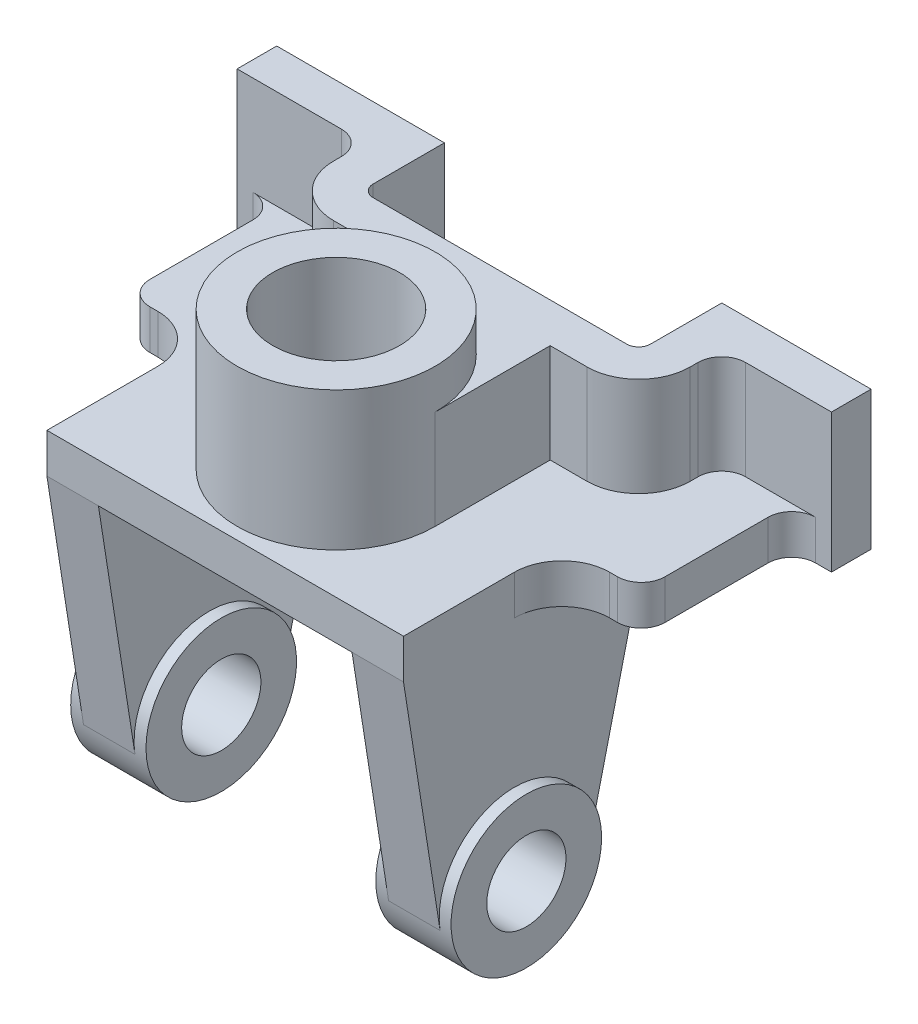
SolidWorks part; units mm, degrees
ref_plane "Front Plane" through (0, 0, 0) normal (0, 0, 1) x (1, 0, 0)
ref_plane "Top Plane" through (0, 0, 0) normal (0, 1, 0) x (1, 0, 0)
ref_plane "Right Plane" through (0, 0, 0) normal (1, 0, 0) x (0, 0, -1)
sketch "Sketch1" plane through (0, 0, 0) normal (0, 1, 0) x (1, 0, 0)
  line L1 (-45, -44) -> (45, -44)
  line L3 (-75, 44) -> (-32.6781, 44)
  line L7 (65, 2) -> (65, 28)
  line L9 (-65, 2) -> (-65, 28)
  line L10 (-71, 34) -> (-75, 34)
  line L11 (71, 34) -> (75, 34)
  line L12 (37.3219, 44) -> (75, 44)
  line L17 (65, -34) -> (65, 34) construction
  line L18 (-65, -34) -> (-65, 34) construction
  line L19 (-75, 34) -> (-71, 34)
  line L20 (-75, 44) -> (75, 44) construction
  line L22 (-65, 34) -> (65, 34) construction
  line L23 (-32.6781, 44) -> (-32.6781, 26.013)
  line L24 (-29.6781, 23.013) -> (34.3219, 23.013)
  line L25 (37.3219, 44) -> (37.3219, 26.013)
  line L26 (75, 34) -> (53.3219, 34)
  line L27 (-48.6781, 34) -> (-75, 34)
  line L28 (-59, -4) -> (-57, -4)
  line L29 (-65, 2) -> (-65, 28)
  line L31 (65, 2) -> (65, 28)
  line L32 (-75, 34) -> (-75, 44)
  line L35 (-45, -44) -> (45, -44)
  line L36 (-45, -44) -> (-45, -16)
  line L38 (45, -44) -> (45, -16)
  line L39 (75, 34) -> (75, 44)
  line L40 (57, -4) -> (59, -4)
  line L41 (-59, -4) -> (-57, -4)
  line L43 (-75, -44) -> (-75, 44) construction
  line L44 (75, -44) -> (75, 44) construction
  line L45 (-65, -34) -> (65, -34) construction
  line L46 (-75, -44) -> (75, -44) construction
  line L48 (-65, 34) -> (-65, 34)
  line L51 (71, 34) -> (75, 34)
  line L53 (-65, 34) -> (-48.6781, 34)
  line L54 (-42.6781, 28) -> (-42.6781, 26.013)
  line L55 (-29.6781, 13.013) -> (34.3219, 13.013)
  line L56 (47.3219, 28) -> (47.3219, 26.013)
  line L57 (53.3219, 34) -> (65, 34)
  line L58 (65, 34) -> (65, 34)
  line L59 (65, 34) -> (75, 34)
  line L60 (-65, 34) -> (-75, 34)
  line L61 (47.3219, 34) -> (47.3219, 26.013) construction
  line L62 (47.3219, 34) -> (65, 34) construction
  line L63 (-65, 34) -> (-42.6781, 34) construction
  line L64 (-42.6781, 34) -> (-42.6781, 26.013) construction
  line L65 (0, -44) -> (0, 13.013)
  line L66 (0, 44) -> (0, -16)
  line L67 (-25, 13.013) -> (-25, -16)
  line L68 (-25, -16) -> (25, -16)
  line L69 (25, -16) -> (25, 13.013)
  arc A0 (71, 34) -> (65, 28) centre (71, 28) ccw
  arc A1 (-71, 34) -> (-65, 28) centre (-71, 28) cw
  arc A2 (57, -4) -> (45, -16) centre (57, -16) ccw
  arc A3 (-45, -16) -> (-57, -4) centre (-57, -16) ccw
  arc A4 (59, -4) -> (65, 2) centre (59, 2) ccw
  arc A5 (-59, -4) -> (-65, 2) centre (-59, 2) cw
  arc A6 (34.3219, 23.013) -> (37.3219, 26.013) centre (34.3219, 26.013) ccw
  arc A7 (-32.6781, 26.013) -> (-29.6781, 23.013) centre (-29.6781, 26.013) ccw
  arc A8 (-42.6781, 26.013) -> (-29.6781, 13.013) centre (-29.6781, 26.013) ccw
  arc A9 (34.3219, 13.013) -> (47.3219, 26.013) centre (34.3219, 26.013) ccw
  arc A10 (47.3219, 28) -> (53.3219, 34) centre (53.3219, 28) cw
  arc A11 (-48.6781, 34) -> (-42.6781, 28) centre (-48.6781, 28) cw
  circle A12 centre (0, -16) radius 25
  point P0 (0, 0)
  point P10 (0, 46.8521)
  point P23 (0, 46.8521)
  point P25 (0, 15)
  point P31 (0, -24)
  point P39 (-45, -4)
  dimension "D4" = 6
  dimension "D5" = 6
  dimension "D1" = 12
  dimension "D6" = 12
  dimension "D9" = 6
  dimension "D10" = 6
  dimension "D11" = 3
  dimension "D12" = 3
  dimension "D14" = 6
  dimension "D15" = 6
  dimension "D2" = 150
  dimension "D7" = 90
  dimension "D8" = 40
  dimension "D16" = 60
  dimension "D3" = 10
  dimension "D13" = 10
extrude "Boss-Extrude1" add sketch "Sketch1" along normal blind 45 contours A12
extrude "Boss-Extrude2" add sketch "Sketch1<3>" along normal blind 35 contours A12 L69 L55 L66 | A12 L66 L55 L67 | L27 A11 L54 A8 L55 L66 L24 A7 L23 L3 L32 L10 | L56 A10 L26 L11 L39 L12 L25 A6 L24 L66 L55 A9 region at (-16.4564, 0, -6.664) region at (16.4564, 0, -6.664) region at (-37.4943, 0, -28.9801) region at (38.4061, 0, -27.9358)
sketch "Sketch1<3>" plane through (0, 0, 0) normal (0, 1, 0) x (1, 0, 0) same geometry as "Sketch1"
extrude "Boss-Extrude3" add sketch "Sketch1<4>" along normal blind 10 contours A12 L67 L55 A8 L54 A11 L27 A1 L9 A5 L28 A3 L36 L1 L65 | A12 L65 L35 L38 A2 L40 A4 L7 A0 L26 A10 L56 A9 L55 L69 region at (-40.5778, 0, 5.7123) region at (40.437, 0, 7.0555)
sketch "Sketch1<4>" plane through (0, 0, 0) normal (0, 1, 0) x (1, 0, 0) same geometry as "Sketch1"
sketch "Sketch2" plane through (0, 45, 0) normal (0, 1, 0) x (1, 0, 0)
  circle A0 centre (0, -16) radius 16
  dimension "D1" = 32
extrude "Cut-Extrude1" cut sketch "Sketch2" against normal blind 82 contours A0
sketch "Sketch3" plane through (45, 0, 0) normal (1, 0, 0) x (0, 0, -1)
  line L0 (-16, 10) -> (-16, -56)
  line L1 (-16, 10) -> (-16, 45) construction
  line L2 (0, 45) -> (-32, 45) construction
  line L7 (2, 0) -> (28, 0) construction
  line L8 (-44, 0) -> (-34.7713, -58.9392)
  line L9 (17, 0) -> (2.7713, -58.9392)
  line L10 (-44, 0) -> (17, 0)
  circle A0 centre (-16, -56) radius 19
  circle A1 centre (-16, -56) radius 10
  dimension "D4" = 38
  dimension "D5" = 20
  dimension "D1" = 66
extrude "Boss-Extrude6" add sketch "Sketch3" against normal blind 13 contours A0 L0 L8 | A0 L9 L10 L0 | A1 A0 region at (45, -20.273, 1.3091) region at (45, -20.3618, 29.0036) region at (45, -42.945, 2.945)
sketch "Sketch6" plane through (45, 0, 0) normal (1, 0, 0) x (0, 0, -1)
  circle A0 centre (-16, -56) radius 19
  circle A1 centre (-16, -56) radius 10
extrude "Boss-Extrude7" add sketch "Sketch6" along normal blind 3
sketch "Sketch7" plane through (32, 0, 0) normal (-1, 0, 0) x (0, 0, 1)
  circle A0 centre (16, -56) radius 19
  circle A1 centre (16, -56) radius 10
extrude "Boss-Extrude8" add sketch "Sketch7" along normal blind 3
mirror "Mirror1" about plane through (0, 0, 0) normal (1, 0, 0) of "Boss-Extrude8", "Boss-Extrude7", "Boss-Extrude6"
